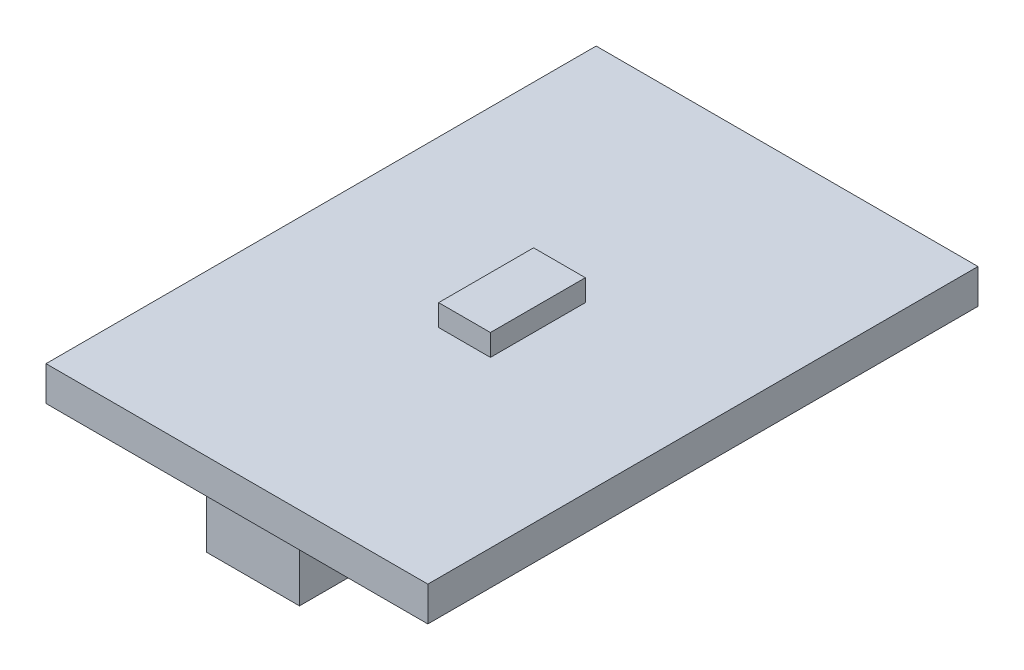
SolidWorks part; units mm, degrees
ref_plane "Front Plane" through (0, 0, 0) normal (0, 0, 1) x (1, 0, 0)
ref_plane "Top Plane" through (0, 0, 0) normal (0, 1, 0) x (1, 0, 0)
ref_plane "Right Plane" through (0, 0, 0) normal (1, 0, 0) x (0, 0, -1)
sketch "SK_Board" plane through (0, 0, 0) normal (0, 1, 0) x (1, 0, 0)
  line L1 (-8.85, 12.75) -> (8.85, 12.75)
  line L2 (-8.85, 12.75) -> (-8.85, -12.75)
  line L3 (-8.85, -12.75) -> (8.85, -12.75)
  line L4 (8.85, 12.75) -> (8.85, -12.75)
  dimension "D1" = 25.5
  dimension "D2" = 17.7
  dimension "D3" = 12.75
  dimension "D4" = 8.85
extrude "EX_Board" add sketch "SK_Board" along normal blind 1.6
ref_plane "PL_Zp1_6" through (0, 1.6, 0) normal (0, 1, 0) x (1, 0, 0)
sketch "SK_Sensor" plane through (0, 1.6, 0) normal (0, 1, 0) x (1, 0, 0)
  line L1 (-1.2, 2.2) -> (1.2, 2.2)
  line L2 (-1.2, 2.2) -> (-1.2, -2.2)
  line L3 (-1.2, -2.2) -> (1.2, -2.2)
  line L4 (1.2, 2.2) -> (1.2, -2.2)
  dimension "D1" = 4.4
  dimension "D2" = 2.4
  dimension "D3" = 2.2
  dimension "D4" = 1.2
extrude "EX_Sensor" add sketch "SK_Sensor" along normal blind 1
sketch "SK_KeepOut_STEMMA" plane through (0, 0, 0) normal (0, 1, 0) x (1, 0, 0)
  line L1 (-2.15, -6) -> (2.15, -6)
  line L2 (-2.15, -6) -> (-2.15, -12)
  line L3 (-2.15, -12) -> (2.15, -12)
  line L4 (2.15, -6) -> (2.15, -12)
  line L6 (-2.15, 12) -> (2.15, 12)
  line L7 (-2.15, 12) -> (-2.15, 6)
  line L8 (-2.15, 6) -> (2.15, 6)
  line L9 (2.15, 12) -> (2.15, 6)
  dimension "D1" = 6
  dimension "D2" = 4.3
  dimension "D3" = 6
  dimension "D4" = 2.15
  dimension "D5" = 6
  dimension "D6" = 4.3
  dimension "D7" = 12
  dimension "D8" = 2.15
extrude "EX_KeepOut_STEMMA" add sketch "SK_KeepOut_STEMMA" against normal blind 3
ref_axis "AX_X" through (0, 0, -14.025) along (0, 0, 1)
ref_axis "AX_Y" through (9.735, 0, 0) along (-1, 0, 0)
ref_axis "AX_Z" through (0, 2.88, 0) along (0, -1, 0)
ref_plane "PL_Zp2_6" through (0, 2.6, 0) normal (0, 1, 0) x (1, 0, 0)
sketch "SK_F_range" plane through (0, 2.6, 0) normal (0, 1, 0) x (1, 0, 0)
  point P0 (0, 0)
